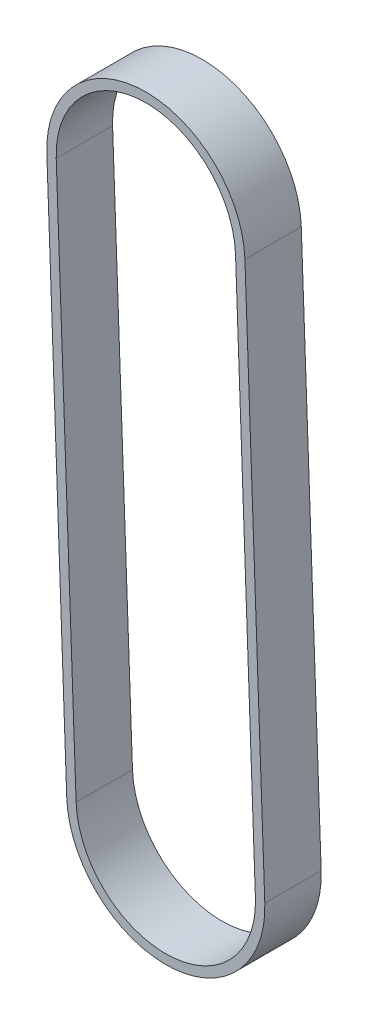
SolidWorks part; units mm, degrees
ref_plane "Front Plane" through (0, 0, 0) normal (0, 0, 1) x (1, 0, 0)
ref_plane "Top Plane" through (0, 0, 0) normal (0, 1, 0) x (1, 0, 0)
ref_plane "Right Plane" through (0, 0, 0) normal (1, 0, 0) x (0, 0, -1)
sketch "Sketch2" plane through (0, 0, 0) normal (0, 0, 1) x (1, 0, 0)
  line L0 (0, 0) -> (1, 0) construction
  line L1 (0, 0) -> (0, 1) construction
  line L4 (14.342, 0.5019) -> (17.517, -86.9405)
  line L5 (-11.112, -87.98) -> (-14.287, -0.5376)
  arc A0 (-14.287, -0.5376) -> (14.342, 0.5019) centre (0.0275, -0.0179) cw
  arc A2 (17.517, -86.9405) -> (-11.112, -87.98) centre (3.2025, -87.4603) cw
extrude "Extrude-Thin1" add sketch "Sketch2" against normal blind 9 thin thin type one direction wall 1.5
